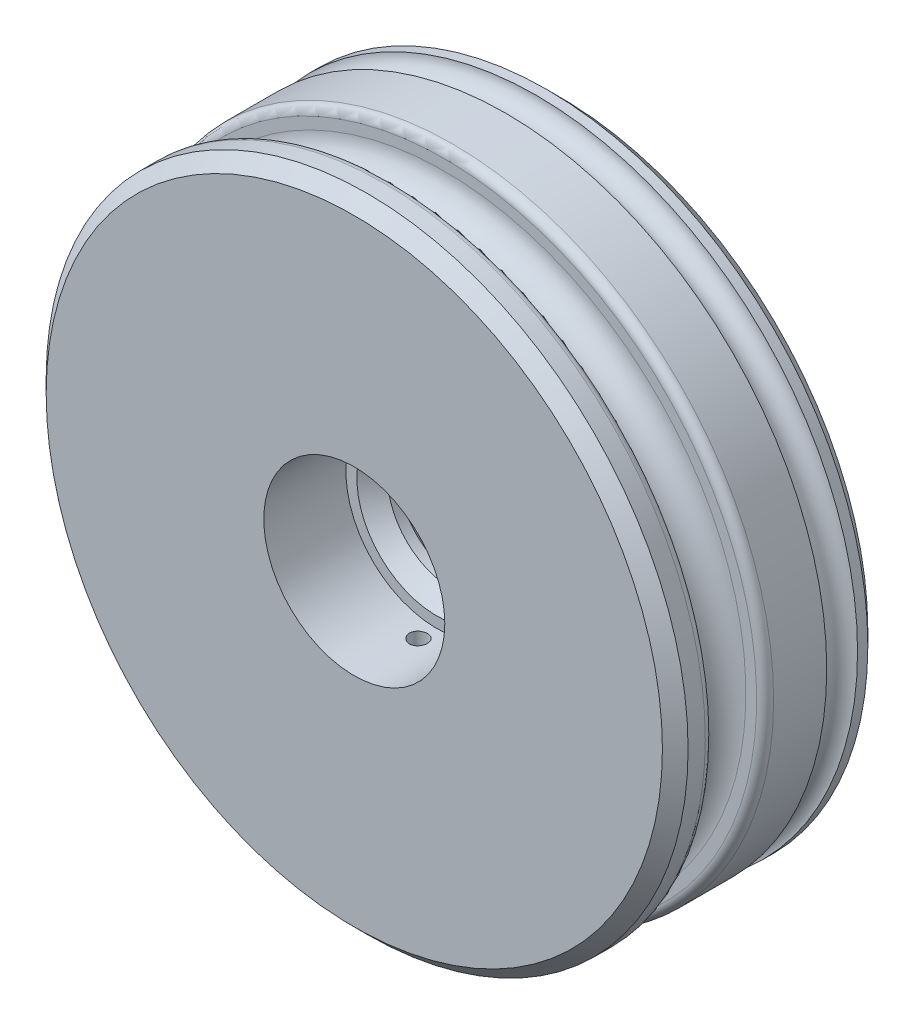
SolidWorks part; units mm, degrees
ref_plane "Front Plane" through (0, 0, 0) normal (0, 0, 1) x (1, 0, 0)
ref_plane "Top Plane" through (0, 0, 0) normal (0, 1, 0) x (1, 0, 0)
ref_plane "Right Plane" through (0, 0, 0) normal (1, 0, 0) x (0, 0, -1)
sketch "Sketch1" plane through (0, 0, 0) normal (0, 0, 1) x (1, 0, 0)
  circle A0 centre (0, 0) radius 12.5
  dimension "D1" = 25
extrude "Boss-Extrude1" add sketch "Sketch1" along normal blind 4
sketch "Sketch3" plane through (0, 0, 0) normal (1, 0, 0) x (0, 0, -1)
  line L1 (-4, 12.5) -> (-4, -12.5) construction
  line L3 (0, 12.5) -> (-4, 12.5) construction
  line L4 (-2.5, 11.75) -> (-2.5, 12.75)
  line L5 (-2.5, 12.75) -> (-0.5, 12.75)
  line L6 (-0.5, 12.75) -> (-0.5, 11.75)
  arc A0 (-2.5, 11.75) -> (-0.5, 11.75) centre (-1.5, 11.75) ccw
  dimension "D1" = 2
  dimension "D2" = 2.5
  dimension "D3" = 0.75
ref_axis "Axis1" through (0, 0, -0.35) along (0, 0, 1)
revolve "Cut-Revolve1" cut sketch "Sketch3" angle 360 about axis through (0, 0, -0.35) along (0, 0, 1)
sketch "Sketch2" plane through (0, 0, 4) normal (0, 0, 1) x (1, 0, 0)
  circle A0 centre (0, 0) radius 3.525
  dimension "D1" = 7.05
extrude "Cut-Extrude1" cut sketch "Sketch2" against normal blind 3.2
chamfer "Chamfer1" distance 0.5 angle 45 1 edges at (12.5, 0, 4)
sketch "Sketch4" plane through (0, 0, 0.8) normal (0, 0, 1) x (1, 0, 0)
  circle A0 centre (0, 0) radius 2.5
  dimension "D1" = 5
extrude "Cut-Extrude2" cut sketch "Sketch4" against normal through all
ref_axis "Axis2" through (0, 55, 4) along (0, -1, 0)
sketch "Sketch6" plane through (0, 0, 0) normal (1, 0, 0) x (0, 0, -1)
  line L0 (-4, 55) -> (-4, -55) construction
  line L1 (-4, 9) -> (-4, 11)
  line L2 (-2.5, 12.5) -> (-3.5, 12.5) construction
  arc A0 (-4, 11) -> (-4, 9) centre (-4, 10) ccw
  dimension "D1" = 2
  dimension "D2" = 2.5
revolve "Revolve1" [suppressed] add sketch "Sketch6" angle 360 about axis through (0, 55, 4) along (0, -1, 0)
chamfer "Chamfer2" distance 0.6 angle 45 1 edges at (2.5, 0, 0.8)
pattern_circular "CirPattern1" [suppressed] count 15 over 360 about axis through (0, 0, -0.35) along (0, 0, 1) reverse direction yes of bodies 110
mirror "Mirror2" about plane through (0, 0, 0) normal (0, 0, 1) of "Cut-Extrude2", "Chamfer1", "Cut-Extrude1", "Boss-Extrude1", "Chamfer2"
sketch "Sketch7" plane through (0, 0, 0) normal (1, 0, 0) x (0, 0, -1)
  line L0 (3.5, 12.5) -> (-0.5, 12.5) construction
  line L1 (3.5, -12.5) -> (3.5, 12.5) construction
  circle A0 centre (2.5, 12.5) radius 0.6
  dimension "D1" = 1.2
  dimension "D2" = 1
revolve "Cut-Revolve3" cut sketch "Sketch7" angle 360 about axis through (0, 0, -0.35) along (0, 0, 1)
fillet "Fillet1" radius 0.33 2 edges at (12.5, 0, 2.5) (-12.5, 0, 0.5)
sketch "Sketch8" plane through (0, 0, 0) normal (0, 1, 0) x (1, 0, 0)
  circle A0 centre (0, -1.5) radius 0.35
  dimension "D1" = 0.7
extrude "Cut-Extrude3" cut sketch "Sketch8" against normal through all
ref_plane "Plane1" through (0, 0, 1.5) normal (0, 0, 1) x (1, 0, 0)
